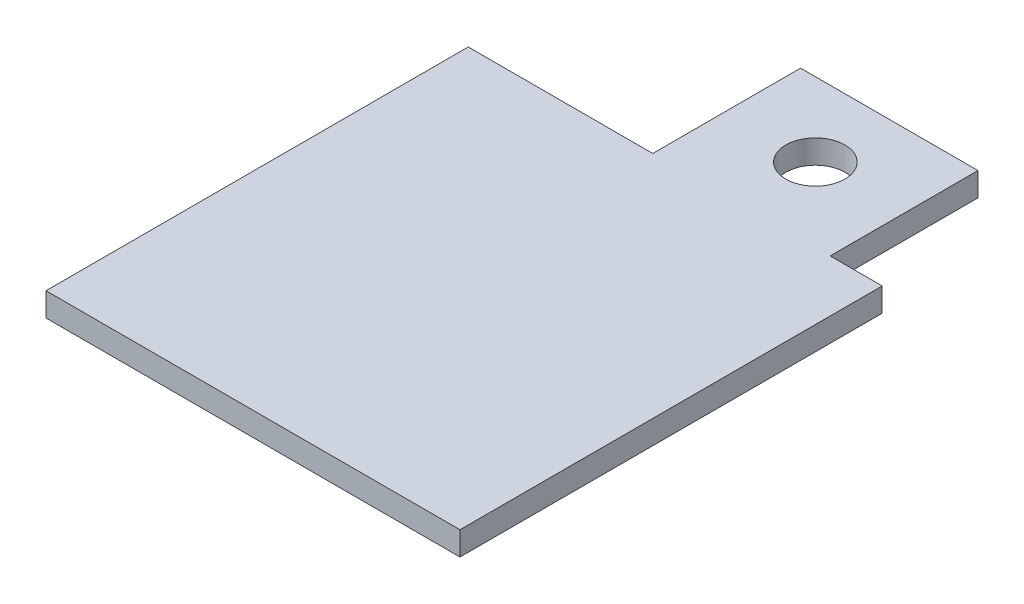
SolidWorks part; units mm, degrees
ref_plane "Front Plane" through (0, 0, 0) normal (0, 0, 1) x (1, 0, 0)
ref_plane "Top Plane" through (0, 0, 0) normal (0, 1, 0) x (1, 0, 0)
ref_plane "Right Plane" through (0, 0, 0) normal (1, 0, 0) x (0, 0, -1)
sketch "Sketch1" plane through (0, 0, 0) normal (0, 1, 0) x (1, 0, 0)
  line L0 (0, 17.5) -> (0, 30) construction
  line L1 (-17.5, -17.5) -> (17.5, -17.5)
  line L2 (-17.5, -17.5) -> (-17.5, 17.5)
  line L3 (-17.5, 17.5) -> (17.5, 17.5)
  line L4 (17.5, -17.5) -> (17.5, 17.5)
  line L5 (-17.5, -17.5) -> (17.5, 17.5) construction
  line L6 (-17.5, 17.5) -> (17.5, -17.5) construction
  line L7 (7.5, 17.5) -> (-7.5, 17.5) construction
  line L8 (-7.5, 17.5) -> (-7.5, 30) construction
  line L9 (7.5, 17.5) -> (7.5, 30)
  line L10 (7.5, 30) -> (-1.9, 30)
  line L11 (7.5, 17.5) -> (13.1, 17.5) construction
  line L12 (13.1, 17.5) -> (13.1, 30)
  line L13 (13.1, 30) -> (7.5, 30)
  line L14 (-7.5, 17.5) -> (-1.9, 17.5) construction
  line L15 (-1.9, 17.5) -> (-1.9, 30)
  line L16 (13.1, 23.75) -> (-1.9, 23.75) construction
  line L17 (-17.5, -17.5) -> (-17.5, -18.2)
  line L18 (-17.5, -18.2) -> (17.5, -18.2)
  line L19 (17.5, -18.2) -> (17.5, -17.5)
  circle A1 centre (0, 23.75) radius 2.5 construction
  circle A2 centre (5.6, 23.75) radius 2.5
  point P0 (0, 0)
  point P11 (0, 17.5)
  dimension "D3" = 5
  dimension "D7" = 5
  dimension "D1" = 35
  dimension "D2" = 12.5
  dimension "D4" = 7.5
  dimension "D5" = 5.6
  dimension "D6" = 5.6
  dimension "D8" = 0.7
extrude "Boss-Extrude1" add sketch "Sketch1" along normal blind 2 contours A2 L9 L3 L12 L13 | A2 L9 L10 L15 L3 | L18 L19 L1 L17 | L1 L4 L3 L2 region at (0, 0, 0) region at (0, 0, 17.85) region at (2.3123, 0, -23.75) region at (10.3497, 0, -23.75)
